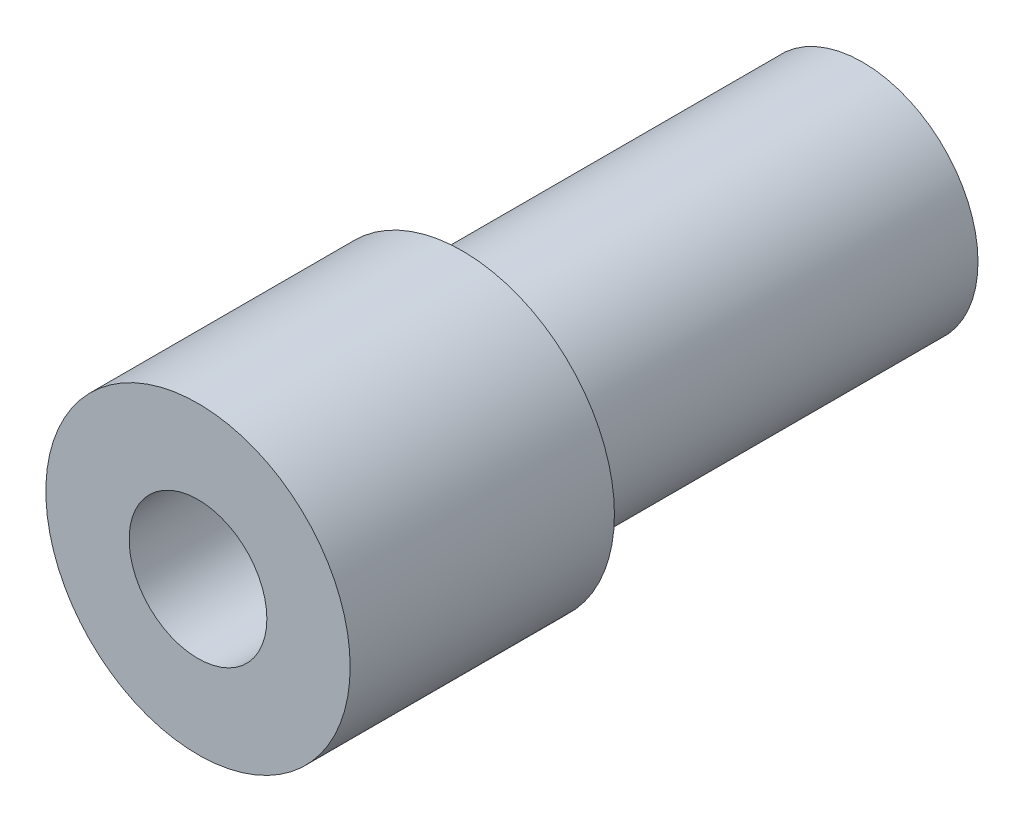
SolidWorks part; units mm, degrees
ref_plane "Спереди" through (0, 0, 0) normal (0, 0, 1) x (1, 0, 0)
ref_plane "Сверху" through (0, 0, 0) normal (0, 1, 0) x (1, 0, 0)
ref_plane "Справа" through (0, 0, 0) normal (1, 0, 0) x (0, 0, -1)
sketch "Эскиз1" plane through (0, 0, 0) normal (0, 0, 1) x (1, 0, 0)
  circle A0 centre (0, 0) radius 14.4
  circle A1 centre (0, 0) radius 8.6
  circle A2 centre (0, 0) radius 16
  circle A3 centre (0, 0) radius 19
  dimension "D1" = 28.8
  dimension "D2" = 17.2
  dimension "D3" = 1.6
  dimension "D4" = 3
extrude "Бобышка-Вытянуть1" add sketch "Эскиз1" against normal blind 80 contours A0 A1 region at (-13.9927, 0, 0)
extrude "Бобышка-Вытянуть2" add sketch "Эскиз1<3>" along normal blind 3 contours A3 A2 | A2 A0 | A0 A1 region at (-13.9927, 0, 0) region at (-15.5475, 0, 0) region at (-18.4626, 0, 0)
sketch "Эскиз1<3>" plane through (0, 0, 0) normal (0, 0, 1) x (1, 0, 0) same geometry as "Эскиз1"
extrude "Бобышка-Вытянуть3" add sketch "Эскиз1<5>" against normal blind 30 contours A3 A2 region at (-18.4626, 0, 0)
sketch "Эскиз1<5>" plane through (0, 0, 0) normal (0, 0, 1) x (1, 0, 0) same geometry as "Эскиз1"
extrude "Бобышка-Вытянуть4" add sketch "Эскиз1<6>" along normal blind 3 from surface contours A1 region at (0, 0, 0) starting at face at (8.6, 0, -80)
sketch "Эскиз1<6>" plane through (0, 0, 0) normal (0, 0, 1) x (1, 0, 0) same geometry as "Эскиз1"
equation "\"DTailTube\"= 16mm'Диаметр трубки хвостового оперения"
equation "\"FusLenght\"= 700mm"
equation "\"DMotor\"= 35.2mm"
equation "\"MotorArm\"= 320mm"
equation "\"DFus\"= 150mm"
equation "\"DFusTube\"= 30mm'Диаметр трубки внутри фюзеляжа"
equation "\"FusTubeHeight\"= 40mm"
equation "\"FusCentralPartLenght\"= 410mm"
equation "\"FusNoseLenght\"= 150mm"
equation "\"WingOffset\"= 1mm'Расстояние от внутренней поверхности фюзеляжа до профиля крыла по вертикали"
equation "\"EllipseRatio\"= 0.95'Центральная часть фюзеляжа - эллипс. Этот параметр - отношение длин осей эллипса"
equation "\"FrameOffset\"= 0.6mm"
equation "\"DThreadedInsert\"= 3.6mm'Внешний диамер резьбовых втулок"
equation "\"CenterSectionLenght\"= 140mm'Длина центроплана"
equation "\"b\"= 1700mm'Размах"
equation "\"cwr\"= 236mm'Корневая хорда крыла"
equation "\"TR\"= 0.75'Сужение крыла"
equation "\"cwt\"= \"TR\" * \"cwr\"'Концевая хорда крыла"
equation "\"DWingMainSpar\"= 16mm'Диаметр главного лонжерона крыла"
equation "\"DWingSecondSpar\"= 8mm'Диаметр второго лонжерона крыла"
equation "\"WingSparsDistance\"= 80mm'Расстояния между отверстиями по лонжерон крыла"
equation "\"c\"= 210mm'САХ крыла"
equation "\"FusTubeLenght\"= \"FusLenght\"-50mm'Длина трубки фюзеляжа"
equation "\"bt\"=291mm'Высота лопатки хвоста"
equation "\"ct\"=182mm'Корневая хорда хвоста"
equation "\"lambda_t\"=0.3'Доля хвоста, занатая рулем высоты"
equation "\"TailTubeLenght\"=730mm'Длина хвостовой балки"
equation "\"DStringer\"=6mm'Диаметр стрингеров"
equation "\"TailConnectorBaseLenght\"=20mm'Высота основания конектора хвоста"
equation "\"CargoHolderHoleDistance\"=30mm'Расстояние между крепежными отверстиями для держателя груза"
equation "\"FuselageThickness\"=1.2mm'Толщина фюзеляжа"
equation "\"DTailSpar\"=6mm'Диаметр лонжерона хвостового оперения"
equation "\"TailSparDistance\"=40mm'Расстояние между лонжеронами хвостового оперения"
equation "\"CrossSectionWidth\"=15mm'Ширина кольцевой части шпангоута"
equation "\"D1@Эскиз1\"=\"DFusTube\"-1.2"
equation "\"D2@Эскиз1\"=\"DTailTube\"+1.2"
